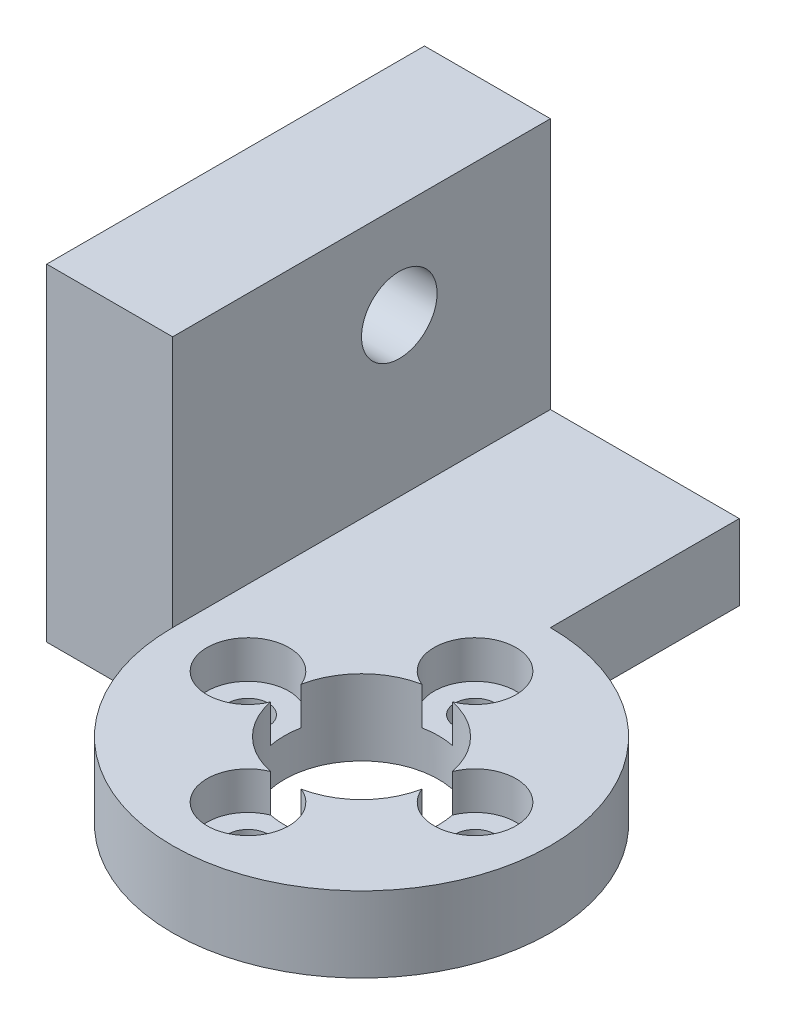
SolidWorks part; units mm, degrees
ref_plane "Front Plane" through (0, 0, 0) normal (0, 0, 1) x (1, 0, 0)
ref_plane "Top Plane" through (0, 0, 0) normal (0, 1, 0) x (1, 0, 0)
ref_plane "Right Plane" through (0, 0, 0) normal (1, 0, 0) x (0, 0, -1)
sketch "Sketch1" plane through (0, 0, 0) normal (0, 1, 0) x (1, 0, 0)
  circle A0 centre (0, 0) radius 15
  dimension "D1" = 30
extrude "Boss-Extrude1" add sketch "Sketch1" along normal blind 6
sketch "Sketch2" plane through (0, 6, 0) normal (0, 1, 0) x (1, 0, 0)
  circle A0 centre (0, 0) radius 6.125
  dimension "D1" = 12.25
extrude "Cut-Extrude1" cut sketch "Sketch2" against normal up to next
hole_wizard "CBORE for M3 SHCS2" positions "Sketch3" profile "Sketch5" counterbore size "M3" standard "ANSI Metric" end condition up to next
sketch "Sketch3" plane through (0, 6, 0) normal (0, 1, 0) x (1, 0, 0)
  point P0 (0, 9.017)
  dimension "D1" = 9.017
sketch "Sketch5" plane through (0, 6, -9.017) normal (1, 0, 0) x (0, 0, 1)
  line L0 (0, 0) -> (0, 6)
  line L1 (0, 6) -> (1.6, 6)
  line L3 (1.6, 6) -> (1.6, 3)
  line L4 (1.6, 3) -> (3.25, 3)
  line L5 (3.25, 3) -> (3.25, 0)
  line L7 (3.25, 0) -> (0, 0)
  line L11 (0, -6.35) -> (0, 107.95) construction
  dimension "Thru Hole Dia." = 3.2
  dimension "Thru Hole Depth" = 6
  dimension "C'Bore Dia." = 6.5
  dimension "C'Bore Depth" = 3
pattern_circular "CirPattern1" count 4 over 360 about axis through (0, -0.001, 0) along (0, 1, 0) of "CBORE for M3 SHCS2"
sketch "Sketch6" plane through (0, 6, 0) normal (0, 1, 0) x (1, 0, 0)
  line L0 (-25, 0) -> (-25, 15)
  line L1 (-25, 15) -> (0, 15)
  line L2 (-25, 0) -> (-15, 0)
  circle A0 centre (0, 0) radius 15 construction
  arc A1 (0, 15) -> (-15, 0) centre (0, 0) ccw
  dimension "D1" = 25
extrude "Boss-Extrude2" add sketch "Sketch6" against normal up to surface (6 mm away) and the other way blind 20 up to face at (9.017, 0, 1.6)
sketch "Sketch7" plane through (-25, 0, 0) normal (-1, 0, 0) x (0, 0, 1)
  line L4 (-15, 6) -> (0, 6)
  line L5 (-15, 26) -> (-15, 6)
  line L6 (0, 26) -> (-15, 26)
  line L7 (0, 6) -> (0, 26)
  line L8 (-15, 6) -> (0, 6)
  line L9 (-15, 26) -> (-15, 6)
  line L10 (0, 26) -> (-15, 26)
  line L11 (0, 6) -> (0, 26)
  dimension "D1" = 0
extrude "Cut-Extrude2" cut sketch "Sketch7" against normal up to next from vertex starting at point (-15, 26, 0)
sketch "Sketch9" plane through (0, 0, -15) normal (0, 0, -1) x (-1, 0, 0)
  line L6 (15, 26) -> (15, 6)
  line L7 (15, 6) -> (0, 6)
  line L8 (0, 6) -> (0, 0)
  line L9 (0, 0) -> (25, 0)
  line L10 (25, 0) -> (25, 26)
  line L11 (25, 26) -> (15, 26)
  line L12 (15, 26) -> (15, 6)
  line L13 (15, 6) -> (0, 6)
  line L14 (0, 6) -> (0, 0)
  line L15 (0, 0) -> (25, 0)
  line L16 (25, 0) -> (25, 26)
  line L17 (25, 26) -> (15, 26)
  dimension "D1" = 0
extrude "Boss-Extrude3" add sketch "Sketch9" along normal blind 15
sketch "Sketch8" plane through (-15, 0, 0) normal (1, 0, 0) x (0, 0, -1)
  line L0 (0, 0) -> (0, 37.894) construction
  line L1 (8, 0) -> (8, 37.894) construction
  line L2 (-15, 0) -> (15, 0) construction
  line L3 (18, 0) -> (18, 37.894) construction
  line L4 (30, 6) -> (15, 6) construction
  circle A0 centre (18, 18.5) radius 10 construction
  circle A1 centre (18, 18.5) radius 3
  dimension "D3" = 12.5
  dimension "D4" = 6
  dimension "D1" = 8
  dimension "D2" = 10
extrude "Cut-Extrude3" cut sketch "Sketch8" against normal up to next
